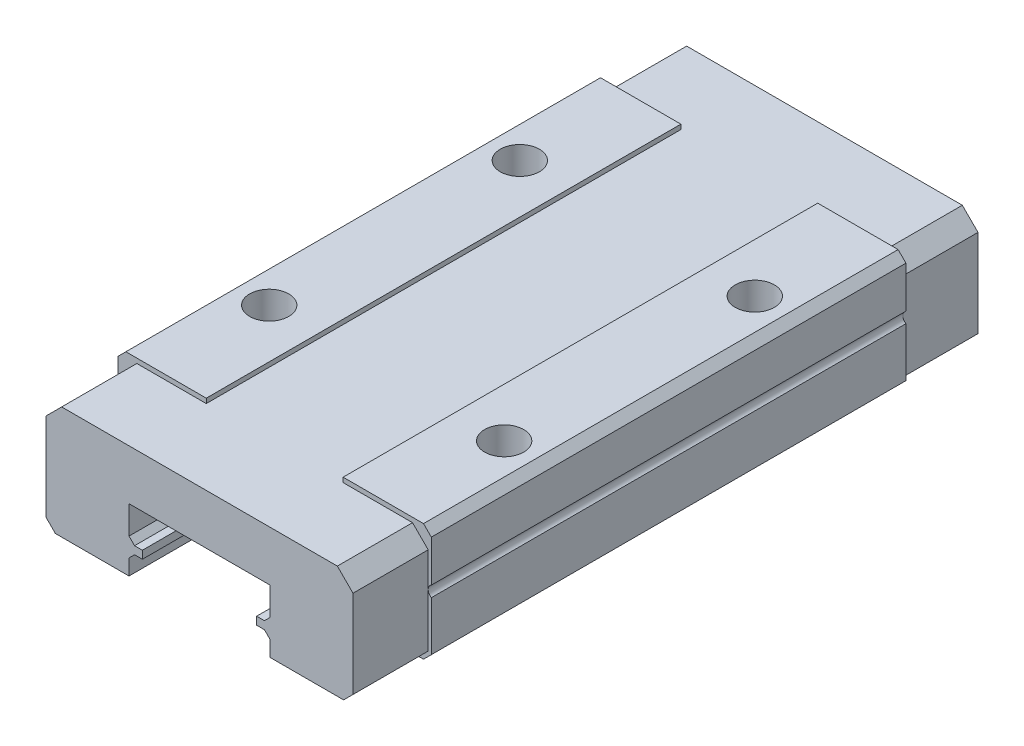
SolidWorks part; units mm, degrees
material "AISI 1020 钢，冷轧"
ref_plane "前视基准面" through (0, 0, 0) normal (0, 0, 1) x (1, 0, 0)
ref_plane "上视基准面" through (0, 0, 0) normal (0, 1, 0) x (1, 0, 0)
ref_plane "右视基准面" through (0, 0, 0) normal (1, 0, 0) x (0, 0, -1)
sketch "草图1" plane through (0, 0, 0) normal (0, 0, 1) x (1, 0, 0)
  line L0 (0, 0) -> (0, 18.7331) construction
  line L1 (-10, 0) -> (-10, 7.5)
  line L2 (4.5, 0) -> (4.5, 1)
  line L3 (4.5, 1) -> (4.1464, 1.3536)
  line L4 (4.1464, 1.3536) -> (3.6464, 1.3536)
  line L5 (3.6464, 1.3536) -> (3.6464, 1.8536)
  line L6 (3.6464, 1.8536) -> (4.1464, 1.8536)
  line L7 (4.1464, 1.8536) -> (4.5, 2.2071)
  line L8 (4.5, 2.2071) -> (4.5, 4)
  line L9 (4.5, 4) -> (-4.5, 4)
  line L10 (4.5, 0) -> (10, 0)
  line L11 (10, 0) -> (10, 7.5)
  line L12 (10, 7.5) -> (-10, 7.5)
  line L13 (-4.5, 0) -> (-10, 0)
  line L14 (-4.5, 2.2071) -> (-4.5, 4)
  line L15 (-4.1464, 1.8536) -> (-4.5, 2.2071)
  line L16 (-3.6464, 1.8536) -> (-4.1464, 1.8536)
  line L17 (-3.6464, 1.3536) -> (-3.6464, 1.8536)
  line L18 (-4.1464, 1.3536) -> (-3.6464, 1.3536)
  line L19 (-4.5, 1) -> (-4.1464, 1.3536)
  line L20 (-4.5, 0) -> (-4.5, 1)
  point P16 (0, 7.5)
  point P19 (0, 4)
  dimension "D1" = 4.5
  dimension "D2" = 1
  dimension "D3" = 0.5
  dimension "D4" = 0.5
  dimension "D5" = 0.5
  dimension "D6" = 4
  dimension "D7" = 10
  dimension "D8" = 7.5
extrude "凸台-拉伸1" add sketch "草图1" against normal blind 39.9
sketch "草图2" plane through (0, 7.5, 0) normal (0, 1, 0) x (1, 0, 0)
  line L0 (0, 39.9) -> (0, 0) construction
  line L1 (10, 39.9) -> (-10, 39.9) construction
  line L2 (10, 19.95) -> (-10, 19.95) construction
  line L3 (10, 39.9) -> (10, 0) construction
  line L4 (-10, 39.9) -> (-10, 0) construction
hole_wizard "M3 螺纹孔1" positions "草图4" profile "草图3" tap size "M3" standard "Gb"
sketch "草图4" plane through (0, 7.5, 0) normal (0, 1, 0) x (1, 0, 0)
  line L0 (0, 39.9) -> (0, 0) construction
  line L1 (10, 19.95) -> (-10, 19.95) construction
  point P0 (7.5, 27.95)
  dimension "D1" = 7.5
  dimension "D2" = 8
sketch "草图3" plane through (7.5, 7.5, -27.95) normal (1, 0, 0) x (0, 0, 1)
  line L0 (0, 0) -> (0, 3.7511)
  line L1 (0, 3.7511) -> (1.25, 3)
  line L2 (1.25, 3) -> (1.25, 0)
  line L5 (1.25, 0) -> (0, 0)
  line L10 (0, 3.7511) -> (-1.25, 3) construction
  line L11 (0, -6.35) -> (0, 107.95) construction
  dimension "螺纹孔钻头直径" = 2.5
  dimension "螺纹孔钻头深度" = 3
  dimension "导头角度" = 118
cosmetic thread "孔螺蚊线1" parameters "D1"=3, "D2"=3
ref_plane "基准面1" through (0, 0, -19.95) normal (0, 0, -1) x (-1, 0, 0)
ref_plane "基准面2" through (0, 0, 0) normal (-1, 0, 0) x (0, 0, 1)
mirror "镜向1" about plane through (0, 0, -19.95) normal (0, 0, -1) of "M3 螺纹孔1"
mirror "镜向2" about plane through (0, 0, 0) normal (-1, 0, 0) of "镜向1"
chamfer "倒角1" distance 0.5 angle 45 2 edges at (10, 7.5, -19.95) (-10, 7.5, -19.95)
sketch "草图5" plane through (0, 7.5, 0) normal (0, 1, 0) x (1, 0, 0)
  line L0 (-9.5, 35.1) -> (-4.3686, 35.1)
  line L1 (-9.5, 39.9) -> (-9.5, 0) construction
  line L2 (-4.3686, 35.1) -> (-4.3686, 4.8)
  line L3 (-4.3686, 4.8) -> (-9.5, 4.8)
  line L4 (0, 39.9) -> (0, -1.0585) construction
  line L5 (9.5, 39.9) -> (-9.5, 39.9) construction
  line L6 (4.3686, 4.8) -> (9.5, 4.8)
  line L7 (4.3686, 35.1) -> (4.3686, 4.8)
  line L8 (9.5, 35.1) -> (4.3686, 35.1)
  line L9 (9.5, 0) -> (-9.5, 0) construction
  line L10 (-9.5, 35.1) -> (-10, 35.1)
  line L11 (-10, 0) -> (-10, 39.9) construction
  line L12 (-10, 35.1) -> (-10, 39.9)
  line L13 (-10, 39.9) -> (10, 39.9)
  line L14 (10, 39.9) -> (10, 35.1)
  line L15 (10, 39.9) -> (10, 0) construction
  line L16 (10, 35.1) -> (9.5, 35.1)
  line L17 (9.5, 4.8) -> (10, 4.8)
  line L18 (10, 4.8) -> (10, 0)
  line L19 (10, 0) -> (-10, 0)
  line L20 (-10, 0) -> (-10, 4.8)
  line L21 (-10, 4.8) -> (-9.5, 4.8)
  dimension "D1" = 4.8
  dimension "D2" = 4.8
extrude "切除-拉伸1" cut sketch "草图5" against normal blind 0.3
sketch "草图6" plane through (0, 7.2, 0) normal (0, 1, 0) x (1, 0, 0)
  line L0 (-10, 39.9) -> (-9.8, 39.9)
  line L1 (9.8, 39.9) -> (-9.8, 39.9) construction
  line L2 (-9.8, 39.9) -> (-9.8, 35.1)
  line L3 (-9.8, 35.1) -> (-10, 35.1)
  line L4 (-10, 0) -> (-10, 39.9) construction
  line L5 (-10, 35.1) -> (-10, 39.9)
  line L6 (0, 39.9) -> (0, 0) construction
  line L7 (-10, 19.95) -> (10, 19.95) construction
  line L8 (10, 39.9) -> (10, 0) construction
  line L9 (10, 35.1) -> (10, 39.9)
  line L10 (9.8, 35.1) -> (10, 35.1)
  line L11 (9.8, 39.9) -> (9.8, 35.1)
  line L12 (10, 39.9) -> (9.8, 39.9)
  line L13 (10, 0) -> (9.8, 0)
  line L14 (9.8, 0) -> (9.8, 4.8)
  line L15 (9.8, 4.8) -> (10, 4.8)
  line L16 (10, 4.8) -> (10, 0)
  line L17 (-10, 4.8) -> (-10, 0)
  line L18 (-9.8, 4.8) -> (-10, 4.8)
  line L19 (-9.8, 0) -> (-9.8, 4.8)
  line L20 (-10, 0) -> (-9.8, 0)
extrude "切除-拉伸2" cut sketch "草图6" against normal blind 8.3
chamfer "倒角2" distance 1 angle 45 4 edges at (-9.8, 7.2, -37.5) (9.8, 7.2, -37.5) (9.8, 7.2, -2.4) (-9.8, 7.2, -2.4)
chamfer "倒角3" distance 0.6 angle 45 4 edges at (9.8, 0, -2.4) (-9.8, 0, -2.4) (-9.8, 0, -37.5) (9.8, 0, -37.5)
chamfer "倒角4" distance 0.5 angle 45 2 edges at (10, 0, -19.95) (-10, 0, -19.95)
sketch "草图7" plane through (0, 0, -35.1) normal (0, 0, -1) x (-1, 0, 0)
  line L0 (-9.8, 0.6) -> (-9.8, 6.2) construction
  line L1 (-4.5, 0) -> (-9.2, 0) construction
  circle A0 centre (-10.2, 4) radius 0.4
  dimension "D1" = 0.8
  dimension "D2" = 0.4
  dimension "D3" = 4
extrude "切除-拉伸3" cut sketch "草图7" against normal up to surface (30.3 mm away) up to face at (8.6488, 4.6273, -4.8)
sketch "草图9" plane through (0, 0, -39.9) normal (0, 0, -1) x (-1, 0, 0)
  line L0 (0, 7.2) -> (0, 4)
  line L1 (-8.8, 7.2) -> (8.8, 7.2) construction
  line L2 (4.5, 4) -> (-4.5, 4) construction
  line L3 (0, 4) -> (4.5, 4)
